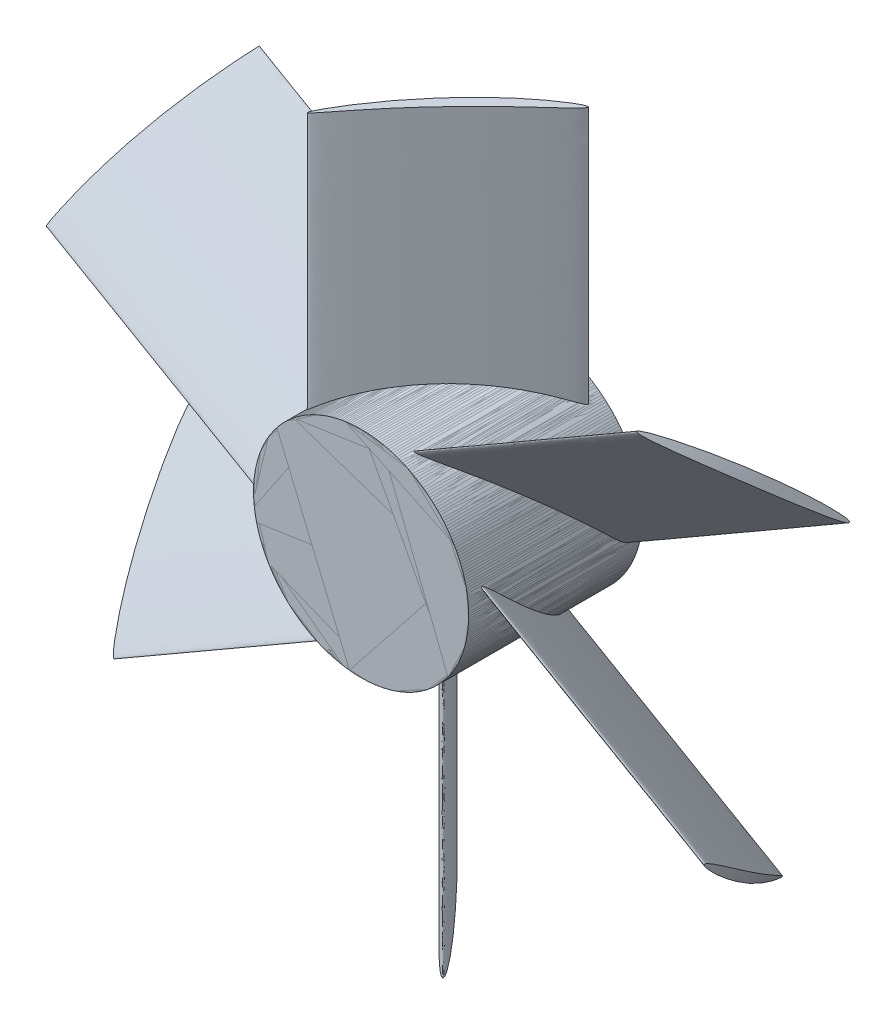
SolidWorks part; units mm, degrees
ref_plane "Alzado" through (0, 0, 0) normal (0, 0, 1) x (1, 0, 0)
ref_plane "Planta" through (0, 0, 0) normal (0, 1, 0) x (1, 0, 0)
ref_plane "Vista lateral" through (0, 0, 0) normal (1, 0, 0) x (0, 0, -1)
sketch "Croquis1" plane through (0, 0, 0) normal (0, 0, 1) x (1, 0, 0)
  circle A0 centre (0, 0) radius 13
  dimension "D1" = 26
extrude "Saliente-Extruir1" add sketch "Croquis1" along normal blind 21
ref_plane "Plano1" through (0, 13, 0) normal (0, 1, 0) x (1, 0, 0)
ref_axis "Eje1" through (0, 0, -1.05) along (0, 0, 1)
sketch "Croquis2" [suppressed] plane through (0, 0, 0) normal (0, 1, 0) x (1, 0, 0)
  line L0 (4.5046, -6.7202) -> (-4.5046, -14.2798) construction
  line L1 (-13, -21) -> (13, -21) construction
  line L2 (0, 0) -> (0, -21) construction
  ellipse E0 centre (0, -10.5) end of major axis (-7.2774, -16.6065) minor radius 0.75
  point P9 (0, -10.5)
  dimension "D1" = 9.5
  dimension "D2" = 0.75
  dimension "D3" = 40
  dimension "D4" = 21
ref_plane "Plano2" through (0, 42, 0) normal (0, 1, 0) x (1, 0, 0)
sketch "Croquis3" [suppressed] plane through (0, 42, 0) normal (0, 1, 0) x (1, 0, 0)
  line L1 (9.5756, -2.4652) -> (-7.2774, -16.6065) construction
  line L3 (-13, -21) -> (13, -21) construction
  ellipse E0 centre (1.1491, -9.5358) end of major axis (9.5756, -2.4652) minor radius 0.3
  dimension "D1" = 40
  dimension "D2" = 22
  dimension "D3" = 0.3
ref_plane "Plano3" [suppressed] through (5.1702, 0, 6.1617) normal (-0.6428, 0, -0.766) x (-0.766, 0, 0.6428)
sketch "Croquis11" [suppressed] plane through (0, 42, 0) normal (0, 1, 0) x (1, 0, 0)
  line L0 (-7.2774, -16.6065) -> (9.6447, -2.4071) construction
  line L1 (-13, -21) -> (13, -21) construction
  ellipse E0 centre (1.1837, -9.5068) end of major axis (-7.2774, -16.6065) minor radius 0.25
  dimension "D1" = 40
sketch "Croquis5" [suppressed] plane through (5.1702, 0, 6.1617) normal (-0.6428, 0, -0.766) x (-0.766, 0, 0.6428)
  line L0 (16.2493, 0) -> (16.2493, 42)
  line L1 (-2.7507, 0) -> (-5.841, 42)
loft "Recubrir2" [suppressed] add profiles "Croquis3", "Croquis2"
sketch "Croquis9" [suppressed] plane through (0, 13, 0) normal (0, 1, 0) x (1, 0, 0)
  line L0 (0, 0) -> (0, -21) construction
  ellipse E0 centre (0, -10.5) end of major axis (7.2774, -4.3935) minor radius 0.75
  dimension "D1" = 21
extrude "Saliente-Extruir3" [suppressed] add sketch "Croquis9" against normal up to body separate body
other "Flexionar1" [suppressed] parameters "D0"=20, "D1"=26, "D2"=0
other "Flexionar2" [suppressed] parameters "D0"=15, "D1"=13.5, "D2"=0
curve "Curva1" [suppressed]
sketch "Croquis2<8>" [suppressed] plane through (0, 0, 0) normal (0, 1, 0) x (1, 0, 0) same geometry as "Croquis2"
sketch "Croquis12" plane through (0, 13, 0) normal (0, 1, 0) x (1, 0, 0)
  line L0 (0, 0) -> (0, -21) construction
  line L1 (0, -10.5) -> (8.184, -1.7238) construction
  line L2 (-13, -21) -> (13, -21) construction
  ellipse E0 centre (0, -10.5) end of major axis (8.184, -1.7238) minor radius 0.66
  dimension "D1" = 47
extrude "Saliente-Extruir4" add sketch "Croquis12" along normal up to surface (29 mm away) and the other way blind 10 up to plane "Plano2"
pattern_circular "MatrizC5" count 6 every 60 about axis through (0, 0, -1.05) along (0, 0, 1) of bodies 110
sketch "Croquis13" plane through (0, 0, 0) normal (0, 0, 1) x (1, 0, 0)
  circle A0 centre (0, 0) radius 42
extrude "Cortar-Extruir1" cut sketch "Croquis13" along normal blind 50 flip side to cut
